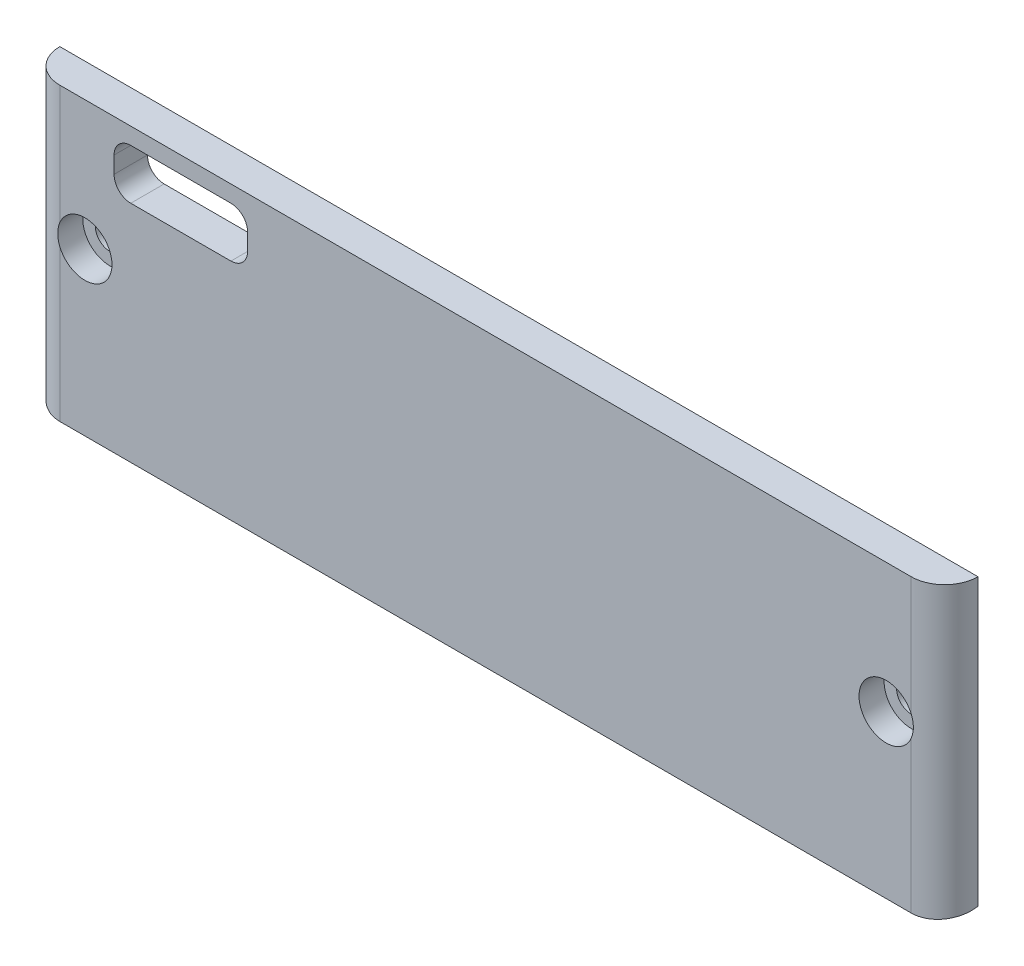
SolidWorks part; units mm, degrees
ref_plane "Plan de face" through (0, 0, 0) normal (0, 0, 1) x (1, 0, 0)
ref_plane "Plan de dessus" through (0, 0, 0) normal (0, 1, 0) x (1, 0, 0)
ref_plane "Plan de droite" through (0, 0, 0) normal (1, 0, 0) x (0, 0, -1)
sketch "Esquisse1" plane through (0, 0, 0) normal (0, 0, 1) x (1, 0, 0)
  line L1 (0, 0) -> (110, 0)
  line L2 (0, 0) -> (0, 34.19)
  line L3 (0, 34.19) -> (110, 34.19)
  line L4 (110, 0) -> (110, 34.19)
  dimension "D1" = 34.19
  dimension "D2" = 110
extrude "Boss.-Extru.1" add sketch "Esquisse1" along normal blind 4
sketch "Esquisse2" plane through (110, 0, 0) normal (1, 0, 0) x (0, 0, -1)
  line L0 (0, 0) -> (-4, 0)
  line L1 (-4, 0) -> (-4, -0.7053)
  line L2 (-4, -0.7053) -> (0, 0)
  dimension "D1" = 10
extrude "Boss.-Extru.2" add sketch "Esquisse2" against normal blind 110
sketch "Esquisse3" plane through (0, 0, 4) normal (0, 0, 1) x (1, 0, 0)
  line L0 (110, -0.7053) -> (110, 34.19) construction
  line L1 (0, 34.19) -> (0, -0.7053) construction
  line L2 (110, 34.19) -> (0, 34.19) construction
  circle A0 centre (7, 18.69) radius 1.75
  circle A1 centre (103, 18.69) radius 1.75
  dimension "D1" = 3.5
  dimension "D2" = 3.5
  dimension "D3" = 7
  dimension "D4" = 7
  dimension "D5" = 15.5
  dimension "D6" = 15.5
extrude "Enlèv. mat.-Extru.1" cut sketch "Esquisse3" against normal blind 4
sketch "Esquisse4" plane through (0, 0, 4) normal (0, 0, 1) x (1, 0, 0)
  circle A0 centre (7, 18.69) radius 3.25
  circle A1 centre (103, 18.69) radius 3.25
  dimension "D1" = 6.5
  dimension "D2" = 6.5
extrude "Enlèv. mat.-Extru.2" cut sketch "Esquisse4" against normal blind 3
sketch "Esquisse5" plane through (0, 0, 4) normal (0, 0, 1) x (1, 0, 0)
  line L0 (110, 34.19) -> (0, 34.19) construction
  line L1 (12.5, 32.19) -> (24.5, 32.19)
  line L2 (10.5, 30.19) -> (10.5, 28.19)
  line L3 (12.5, 26.19) -> (24.5, 26.19)
  line L4 (26.5, 30.19) -> (26.5, 28.19)
  line L5 (0, 34.19) -> (0, -0.7053) construction
  arc A0 (10.5, 30.19) -> (12.5, 32.19) centre (12.5, 30.19) cw
  arc A1 (24.5, 26.19) -> (26.5, 28.19) centre (24.5, 28.19) ccw
  arc A2 (12.5, 26.19) -> (10.5, 28.19) centre (12.5, 28.19) cw
  arc A3 (24.5, 32.19) -> (26.5, 30.19) centre (24.5, 30.19) cw
  dimension "D1" = 2
  dimension "D2" = 6
  dimension "D3" = 16
  dimension "D4" = 2
  dimension "D5" = 10.5
extrude "Enlèv. mat.-Extru.3" cut sketch "Esquisse5" against normal blind 4
fillet "Congé1" radius 4 2 edges at (0, 16.7423, 4) (110, 16.7423, 4)
